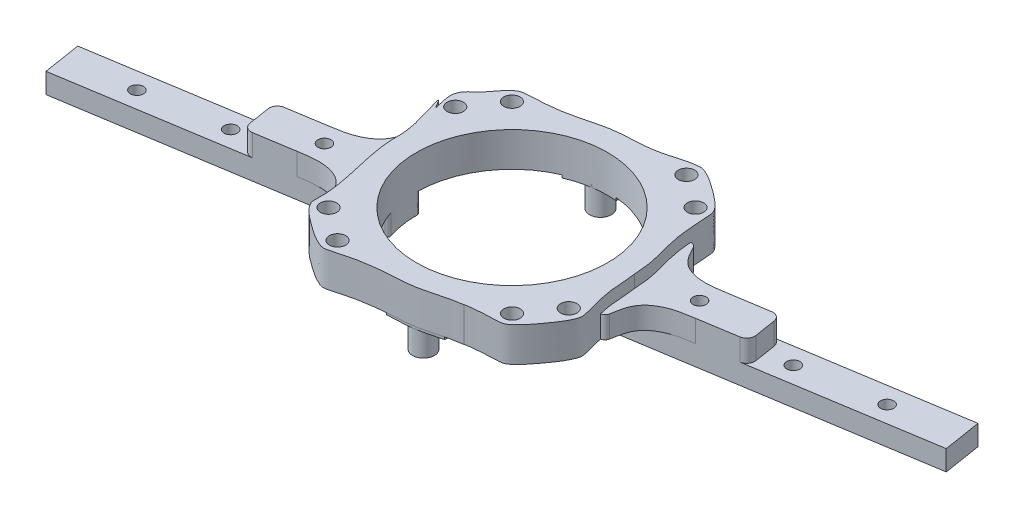
SolidWorks part; units mm, degrees
ref_plane "前视基准面" through (0, 0, 0) normal (0, 0, 1) x (1, 0, 0)
ref_plane "上视基准面" through (0, 0, 0) normal (0, 1, 0) x (1, 0, 0)
ref_plane "右视基准面" through (0, 0, 0) normal (1, 0, 0) x (0, 0, -1)
sketch "草图1" plane through (0, 0, 0) normal (0, 1, 0) x (1, 0, 0)
  circle A0 centre (0, 0) radius 17.5
  circle A1 centre (0, 0) radius 18.901
  dimension "D1" = 35
extrude "凸台-拉伸1" add sketch "草图1" along normal blind 2
sketch "草图2" plane through (0, 0, 0) normal (0, -1, 0) x (1, 0, 0)
  circle A0 centre (-10.7739, 21.1656) radius 1.5
  circle A1 centre (16.8004, 16.7872) radius 1.5
  circle A2 centre (21.1656, 10.7739) radius 1.5
  circle A3 centre (16.7872, -16.8004) radius 1.5
  circle A4 centre (10.7739, -21.1656) radius 1.5
  circle A5 centre (-16.8004, -16.7872) radius 1.5
  circle A6 centre (-21.1656, -10.7739) radius 1.5
  circle A7 centre (-16.7872, 16.8004) radius 1.5
  circle A28 centre (0, 0) radius 17.5
  spline S3 degree 3 poles (11.007, 19.7796) (11.3114, 19.6784) (14.2307, 19.3249) (16.1426, 19.3879) (17.8124, 19.1708) (19.4344, 17.903) (21.2548, 15.4236) (23.0457, 12.9332) (23.7495, 10.9887) (23.274, 8.5261) (21.9734, 4.7628) (22.0269, 1.1873) (21.7447, -0.683) knots 0 0 0 0 0.101498 0.202996 0.236379 0.269761 0.41266 0.555558 0.58894 0.622323 0.811161 1 1 1 1
  spline S4 degree 3 poles (21.7447, -0.683) (21.6101, -1.5752) (21.6055, -3.3542) (20.6884, -6.8809) (19.4904, -11.3054) (19.4855, -15.3122) (19.178, -17.8032) (17.9056, -19.4334) (15.4365, -21.2528) (12.9718, -22.9922) (11.1783, -23.6905) (8.6855, -23.5473) (4.924, -21.9674) (0.2192, -21.8124) (-3.3386, -21.5662) (-6.4463, -20.811) (-9.0785, -20.0903) (-12.7412, -19.4848) (-15.1253, -19.3752) (-17.5836, -19.2474) (-19.4002, -18.127) (-20.9244, -15.1209) (-24.3676, -13.3124) (-22.2966, -7.7817) (-24.7387, -12.2711) (-21.435, -3.3276) (-22.0126, 0.3206) (-20.5515, 8.1406) (-19.1109, 13.0019) (-19.2816, 16.8284) knots 0 0 0 0 0.02817 0.053916 0.112305 0.168269 0.178162 0.188055 0.230405 0.272754 0.280796 0.288838 0.34856 0.404524 0.432694 0.45844 0.502911 0.516855 0.572819 0.576577 0.592462 0.634812 0.677161 0.707499 0.719914 0.775878 0.831843 0.888071 1 1 1 1
  spline S5 degree 3 poles (-19.2816, 16.8284) (-19.323, 17.5174) (-18.1907, 19.2578) (-15.4061, 21.2421) (-12.9273, 23.0421) (-10.9838, 23.7431) (-9.3566, 23.4387) (-7.2233, 22.7077) (-4.4614, 22.2162) (-1.8337, 21.8607) (0.7732, 21.7432) (3.3794, 21.5754) (7.3403, 20.5662) (8.6858, 20.19) (9.8558, 19.9936) (10.7406, 19.8682) (11.007, 19.7796) knots 0 0 0 0 0.047987 0.150696 0.253406 0.277399 0.301393 0.374345 0.447298 0.510152 0.573007 0.641327 0.709648 0.853023 0.882058 1 1 1 1
  dimension "D1" = 3
extrude "凸台-拉伸2" add sketch "草图2" along normal blind 4.3 and the other way blind 2
sketch "草图3" plane through (0, -4.3, 0) normal (0, -1, 0) x (1, 0, 0)
  line L0 (12.149, 8.7024) -> (-39.7791, 16.948) construction
  line L1 (3.0581, 19.2587) -> (0, 0) construction
  line L2 (0, 0) -> (-3.0579, -19.2577) construction
  line L3 (-12.2524, -8.685) -> (39.6757, -16.9305) construction
  circle A0 centre (3.0581, 19.2587) radius 2
  circle A1 centre (3.0581, 19.2587) radius 9 construction
  circle A2 centre (-3.0579, -19.2577) radius 2
  circle A3 centre (-3.0579, -19.2577) radius 9 construction
  dimension "D1" = 18
  dimension "D2" = 4
  dimension "D3" = 18
  dimension "D4" = 4
extrude "凸台-拉伸3" add sketch "草图3" along normal blind 5
sketch "草图5" plane through (0, -4.3, 0) normal (0, -1, 0) x (1, 0, 0)
  line L0 (0, 0) -> (38.9853, -6.1904) construction
  line L1 (70.6703, -14.0546) -> (-71.5479, 8.5279) construction
  circle A0 centre (3.0581, 19.2587) radius 5 construction
  arc A1 (-1.5944, 17.4272) -> (6.9144, 16.0761) centre (0, 0) cw
  arc A2 (-2.6852, -17.2928) -> (2.7444, 17.2835) centre (0, 0) ccw construction
  arc A3 (-1.3158, 21.6815) -> (-1.5944, 17.4272) centre (3.0581, 19.2587) ccw
  arc A4 (7.9454, 20.3141) -> (6.9144, 16.0761) centre (3.0581, 19.2587) cw
  arc A5 (-7.9672, -20.2075) -> (-6.9144, -16.0761) centre (-3.0581, -19.2587) cw
  arc A6 (-6.9144, -16.0761) -> (1.5944, -17.4272) centre (0, 0) ccw
  arc A7 (1.262, -21.7761) -> (1.5944, -17.4272) centre (-3.0581, -19.2587) ccw
  spline S0 degree 3 poles (-1.3158, 21.6815) (-0.2135, 21.5939) (1.3807, 21.5885) (3.4585, 21.3907) (5.444, 20.9684) (6.9168, 20.5202) (7.9454, 20.3141) knots 0 0 0 0 0.352817 0.508743 0.665414 1 1 1 1
  spline S2 degree 3 poles (-7.9672, -20.2075) (-6.892, -20.4656) (-5.3746, -20.9543) (-3.3377, -21.4099) (-1.319, -21.6234) (0.2201, -21.6535) (1.262, -21.7761) knots 0 0 0 0 0.352817 0.508743 0.665414 1 1 1 1
  dimension "D1" = 10
extrude "凸台-拉伸5" add sketch "草图5" along normal blind 0.5
sketch "草图6" plane through (0, -4.3, 0) normal (0, -1, 0) x (1, 0, 0)
  line L0 (0, 0) -> (83.2876, -13.2251) construction
  line L1 (70.6703, -14.0546) -> (-71.5479, 8.5279) construction
  line L2 (0, 0) -> (7.0837, 44.6111) construction
  line L3 (22.6545, 6.4264) -> (16.7134, 7.3698)
  line L4 (32.0065, -1.5404) -> (39.048, -2.6585)
  line L5 (71.6577, -7.8366) -> (-70.5606, 14.746) construction
  line L6 (-30.9094, 8.4499) -> (-37.9509, 9.5679)
  line L7 (40.2942, -4.3752) -> (39.9809, -6.3485)
  line L8 (19.5496, -13.1279) -> (13.6084, -12.1845)
  line L9 (30.9094, -8.4499) -> (37.9509, -9.5679)
  line L10 (39.6675, -8.3217) -> (39.9809, -6.3485)
  line L11 (-39.6675, 8.3217) -> (-39.9809, 6.3485)
  line L12 (-40.2942, 4.3752) -> (-39.9809, 6.3485)
  line L13 (-32.0065, 1.5404) -> (-39.048, 2.6585)
  line L14 (-19.5496, 13.1279) -> (-13.6084, 12.1845)
  line L15 (-22.6545, -6.4264) -> (-16.7134, -7.3698)
  circle A0 centre (21.1656, 10.7739) radius 2.5 construction
  arc A1 (1.5944, -17.4272) -> (6.9144, 16.0761) centre (0, 0) ccw construction
  arc A2 (13.3066, -11.3659) -> (16.1729, 6.685) centre (0, 0) ccw
  arc A3 (23.4842, 5.6027) -> (22.6545, 6.4264) centre (22.4977, 5.4388) ccw
  arc A4 (16.7134, 7.3698) -> (16.1729, 6.685) centre (16.6349, 6.876) ccw
  arc A5 (39.048, -2.6585) -> (40.2942, -4.3752) centre (38.8128, -4.14) cw
  arc A6 (13.6084, -12.1845) -> (13.3066, -11.3659) centre (13.6868, -11.6907) cw
  arc A7 (20.5935, -12.6017) -> (19.5496, -13.1279) centre (19.7064, -12.1402) cw
  arc A8 (37.9509, -9.5679) -> (39.6675, -8.3217) centre (38.1861, -8.0865) ccw
  arc A9 (-37.9509, 9.5679) -> (-39.6675, 8.3217) centre (-38.1861, 8.0865) ccw
  arc A10 (-39.048, 2.6585) -> (-40.2942, 4.3752) centre (-38.8128, 4.14) cw
  arc A11 (-20.5935, 12.6017) -> (-19.5496, 13.1279) centre (-19.7064, 12.1402) cw
  arc A12 (-13.6084, 12.1845) -> (-13.3066, 11.3659) centre (-13.6868, 11.6907) cw
  arc A13 (-16.1729, -6.685) -> (-13.3066, 11.3659) centre (0, 0) cw
  arc A14 (-16.7134, -7.3698) -> (-16.1729, -6.685) centre (-16.6349, -6.876) ccw
  arc A15 (-23.4842, -5.6027) -> (-22.6545, -6.4264) centre (-22.6575, -5.5997) ccw
  spline S0 degree 3 poles (20.5935, -12.6017) (20.8165, -12.1731) (21.4171, -11.0059) (22.8603, -8.9685) (26.5188, -7.7575) (29.1956, -8.1777) (30.9094, -8.4499) knots 0.057026 0.057026 0.057026 0.057026 0.169435 0.36028 0.616457 1 1 1 1
  spline S1 degree 3 poles (23.4842, 5.6027) (23.5634, 5.1261) (23.7729, 3.8302) (24.514, 1.446) (27.6174, -0.8387) (30.2927, -1.2683) (32.0065, -1.5404) knots 0.057026 0.057026 0.057026 0.057026 0.169435 0.36028 0.616457 1 1 1 1
  spline S2 degree 3 poles (-23.4842, -5.6027) (-23.5634, -5.1261) (-23.7729, -3.8302) (-24.514, -1.446) (-27.6174, 0.8387) (-30.2927, 1.2683) (-32.0065, 1.5404) knots 0.057026 0.057026 0.057026 0.057026 0.169435 0.36028 0.616457 1 1 1 1
  spline S3 degree 3 poles (-20.5935, 12.6017) (-20.8165, 12.1731) (-21.4171, 11.0059) (-22.8603, 8.9685) (-26.5188, 7.7575) (-29.1956, 8.1777) (-30.9094, 8.4499) knots 0.057026 0.057026 0.057026 0.057026 0.169435 0.36028 0.616457 1 1 1 1
  point P34 (15.8047, 7.514)
  dimension "D1" = 5
  dimension "D2" = 1
  dimension "D3" = 0.5
  dimension "D4" = 1.5
extrude "凸台-拉伸6" add sketch "草图6" against normal blind 4 separate body
sketch "草图7" plane through (0, -4.3, 0) normal (0, -1, 0) x (1, 0, 0)
  line L0 (17.2287, -6.2775) -> (70.5606, -14.746)
  line L1 (17.2287, -6.2775) -> (18.3258, 0.6319) construction
  line L2 (70.5606, -14.746) -> (71.6577, -7.8366)
  line L3 (18.3258, 0.6319) -> (71.6577, -7.8366)
  line L4 (17.2287, -6.2775) -> (71.6577, -7.8366) construction
  line L5 (70.5606, -14.746) -> (18.3258, 0.6319) construction
  line L6 (71.6577, -7.8366) -> (-70.5606, 14.746) construction
  line L7 (71.6266, -8.0321) -> (70.5916, -14.5504) construction
  line L8 (18.3258, 0.6319) -> (18.0775, 0.6713)
  line L9 (17.2287, -6.2775) -> (16.9804, -6.2381)
  line L10 (70.5606, -14.746) -> (-71.6577, 7.8366) construction
  line L11 (0, 0) -> (5.947, 37.4527) construction
  line L12 (-71.6577, 7.8366) -> (-70.5606, 14.746)
  line L13 (-17.2287, 6.2775) -> (-70.5606, 14.746)
  line L14 (-18.3258, -0.6319) -> (-71.6577, 7.8366)
  line L15 (-18.3258, -0.6319) -> (-18.0775, -0.6713)
  line L16 (-17.2287, 6.2775) -> (-16.9804, 6.2381)
  arc A0 (1.5944, -17.4272) -> (6.9144, 16.0761) centre (0, 0) ccw construction
  arc A1 (17.4991, 0.1726) -> (16.585, -5.5847) centre (0, 0) cw
  arc A2 (16.9804, -6.2381) -> (16.585, -5.5847) centre (17.0588, -5.7443) cw
  arc A3 (18.0775, 0.6713) -> (17.4991, 0.1726) centre (17.9991, 0.1775) ccw
  arc A4 (-18.0775, -0.6713) -> (-17.4991, -0.1726) centre (-17.9991, -0.1775) ccw
  arc A5 (-16.9804, 6.2381) -> (-16.585, 5.5847) centre (-17.0588, 5.7443) cw
  arc A6 (-16.585, 5.5847) -> (-17.4991, -0.1726) centre (0, 0) ccw
  point P1 (44.4432, -7.057)
  point P20 (16.3861, -6.1437)
  point P23 (17.4832, 0.7657)
  dimension "D1" = 0.5
extrude "凸台-拉伸7" add sketch "草图7" along normal up to surface (3.7 mm away)
sketch "草图8" plane through (0, -8, 0) normal (0, -1, 0) x (1, 0, 0)
  circle A0 centre (59.2576, -9.4094) radius 1.2
  circle A1 centre (44.4432, -7.057) radius 1.2
  circle A2 centre (29.6288, -4.7047) radius 1.2
  circle A3 centre (-29.6288, 4.7047) radius 1.2
  circle A4 centre (-44.4432, 7.057) radius 1.2
  circle A5 centre (-59.2576, 9.4094) radius 1.2
  dimension "D1" = 2.4
extrude "切除-拉伸1" cut sketch "草图8" against normal through all
